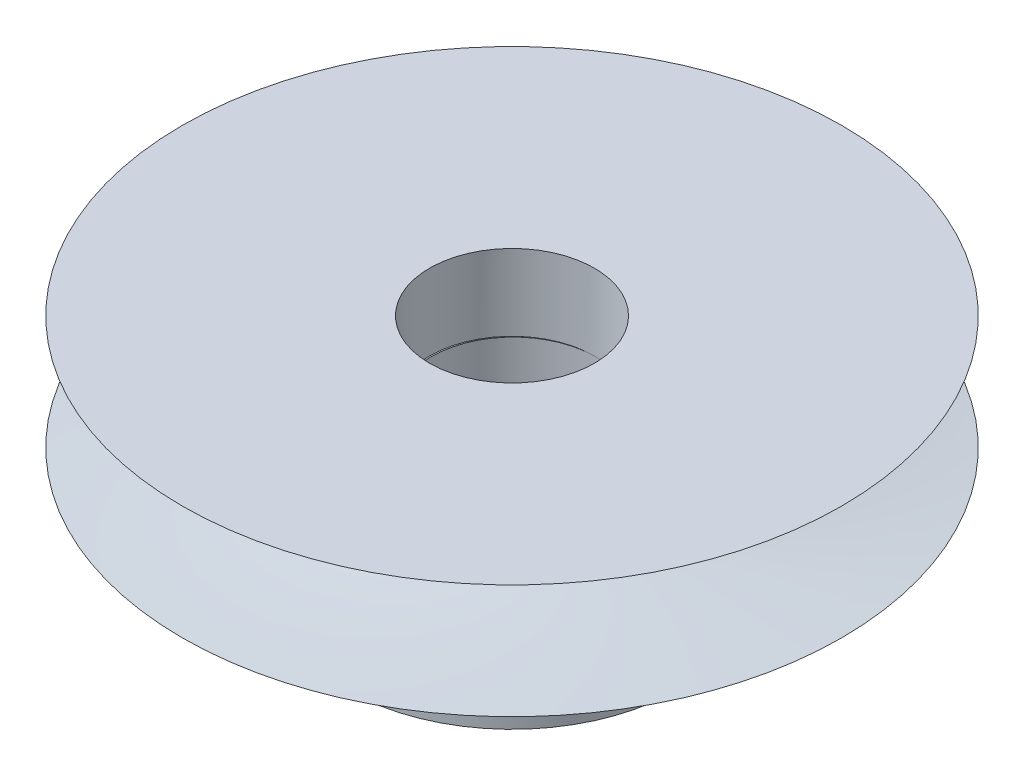
SolidWorks part; units mm, degrees
ref_plane "Front Plane" through (0, 0, 0) normal (0, 0, 1) x (1, 0, 0)
ref_plane "Top Plane" through (0, 0, 0) normal (0, 1, 0) x (1, 0, 0)
ref_plane "Right Plane" through (0, 0, 0) normal (1, 0, 0) x (0, 0, -1)
sketch "Sketch9" plane through (0, 0, 0) normal (0, 0, 1) x (1, 0, 0)
  line L0 (-4.7031, 1.5646) -> (8.2969, -1.4354) construction
  line L1 (-4.7031, -2.9354) -> (8.2969, -2.9354)
  line L3 (-4.7031, 1.5646) -> (8.2969, 1.5646)
  line L4 (8.2969, -2.9354) -> (8.2969, 1.5646)
  line L5 (8.2969, -1.4354) -> (-4.7031, -2.9354) construction
  spline S0 degree 2 poles (-4.7031, 1.5646) (8.2969, -1.4354) (-4.7031, -2.9354) knots 0 0 0 1 1 1
  dimension "D3" = 13
  dimension "D1" = 4.5
  dimension "D2" = 13
revolve "Revolve1" add sketch "Sketch9" angle 360 about L4
sketch "Sketch117" plane through (0, 1.5646, 0) normal (0, 1, 0) x (1, 0, 0)
  circle A0 centre (8.2969, 0) radius 3.25
extrude "Cut-Extrude4" cut sketch "Sketch117" against normal blind 3
sketch "Sketch122" plane through (0, -2.9354, 0) normal (0, -1, 0) x (-1, 0, 0)
  circle A0 centre (-8.2969, 0) radius 6.5398
extrude "Boss-Extrude1" add sketch "Sketch122" along normal blind 5
hole_wizard "M2x0.4 Tapped Hole1" positions "3DSketch1" profile "Sketch124" tap size "M2x0.4" standard "ANSI Metric" end condition through all
sketch3d "3DSketch1"
  circle A0 centre (8.2969, -2.9354, 0) radius 6.5398 construction
  circle A1 centre (8.2969, -7.9354, 0) radius 6.5398 construction
  point P0 (1.8154, -5.4316, -0.8709)
  point P5 (8.2969, -9.4751, 0)
  point P8 (8.2969, -14.4751, 0)
  dimension "D1" = 7
  dimension "D2" = 7.0027
sketch "Sketch124" plane through (1.8154, -5.4316, -0.8709) normal (0, 1, 0) x (-0.1332, 0, 0.9911)
  line L0 (0, 0) -> (0, 21.1551)
  line L1 (0, 21.1551) -> (0.8, 21.1551)
  line L2 (0.8, 21.1551) -> (0.8, 0)
  line L5 (0.8, 0) -> (0, 0)
  line L11 (0, -6.35) -> (0, 107.95) construction
  dimension "Thru Tap Drill Dia." = 1.6
  dimension "Thru Tap Drill Depth" = 21.1551
cosmetic thread "Hole Thread1" parameters "D2"=2
sketch "Sketch125" plane through (0, -1.4354, 0) normal (0, 1, 0) x (1, 0, 0)
  circle A0 centre (8.3503, 0) radius 3.25
extrude "Cut-Extrude5" cut sketch "Sketch125" against normal blind 7
